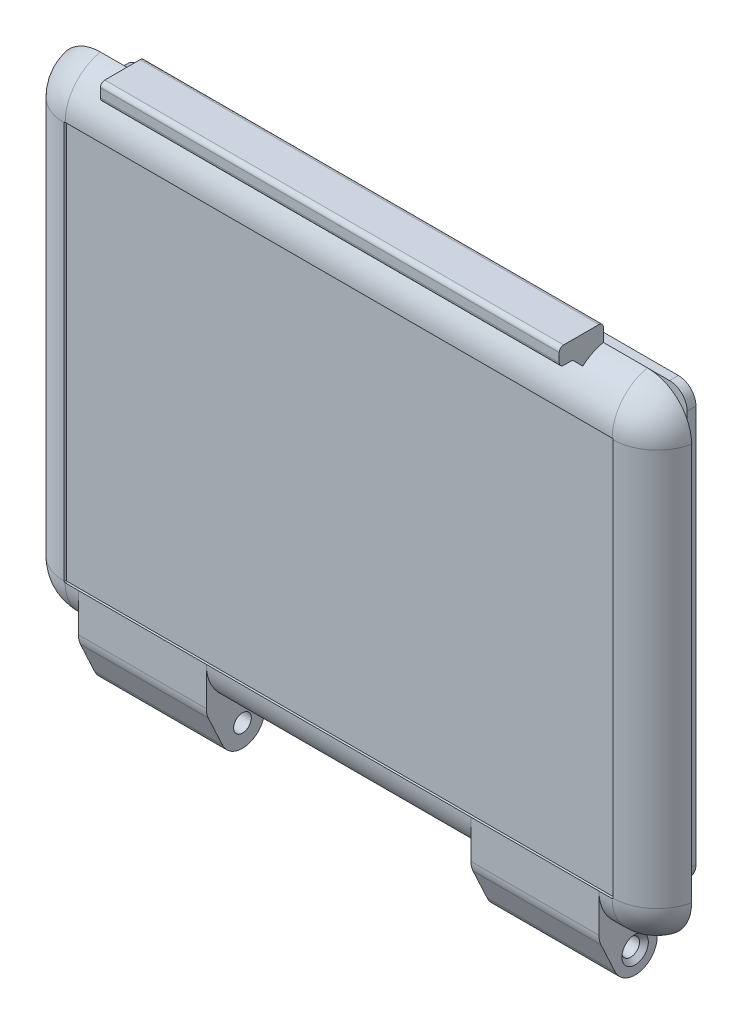
SolidWorks part; units mm, degrees
material "Acrylic (Medium-high impact)"
ref_plane "Front" through (0, 0, 0) normal (0, 0, 1) x (1, 0, 0)
ref_plane "Top" through (0, 0, 0) normal (0, 1, 0) x (1, 0, 0)
ref_plane "Right" through (0, 0, 0) normal (1, 0, 0) x (0, 0, -1)
sketch "Sketch1" plane through (0, 0, 0) normal (0, 0, 1) x (1, 0, 0)
  line L1 (-36, -27.5) -> (36, -27.5)
  line L2 (-36, -27.5) -> (-36, 27.5)
  line L3 (-36, 27.5) -> (36, 27.5)
  line L4 (36, -27.5) -> (36, 27.5)
  line L5 (-36, -27.5) -> (36, 27.5) construction
  line L6 (-36, 27.5) -> (36, -27.5) construction
  point P0 (0, 0)
  dimension "D1" = 72
  dimension "D2" = 55
extrude "Boss-Extrude1" add sketch "Sketch1" along normal blind 4
fillet "Fillet3" radius 5 4 edges at (-36, 27.5, 2) (36, -27.5, 2) (-36, -27.5, 2) (36, 27.5, 2)
fillet "Fillet4" radius 5 8 edges at (34.5355, 26.0355, 4) (36, 0, 4) (34.5355, -26.0355, 4) (0, -27.5, 4) (-34.5355, -26.0355, 4) (-36, 0, 4) (-34.5355, 26.0355, 4) (0, 27.5, 4)
sketch "Sketch2" plane through (0, 0, 4) normal (0, 0, 1) x (1, 0, 0)
  line L4 (31.101, -22.5) -> (31.101, 22.5)
  line L5 (31.101, -22.5) -> (31.101, 22.5)
  line L6 (31, 22.601) -> (-31, 22.601)
  line L7 (31, 22.601) -> (-31, 22.601)
  line L8 (-31.101, 22.5) -> (-31.101, -22.5)
  line L9 (-31.101, 22.5) -> (-31.101, -22.5)
  line L10 (-31, -22.601) -> (31, -22.601)
  line L11 (-31, -22.601) -> (31, -22.601)
  arc A4 (31.101, 22.5) -> (31, 22.601) centre (31, 22.5) ccw
  arc A5 (31.101, 22.5) -> (31, 22.601) centre (31, 22.5) ccw
  arc A6 (-31, 22.601) -> (-31.101, 22.5) centre (-31, 22.5) ccw
  arc A7 (-31, 22.601) -> (-31.101, 22.5) centre (-31, 22.5) ccw
  arc A8 (-31.101, -22.5) -> (-31, -22.601) centre (-31, -22.5) ccw
  arc A9 (-31.101, -22.5) -> (-31, -22.601) centre (-31, -22.5) ccw
  arc A10 (31, -22.601) -> (31.101, -22.5) centre (31, -22.5) ccw
  arc A11 (31, -22.601) -> (31.101, -22.5) centre (31, -22.5) ccw
  dimension "D1" = 0
extrude "Cut-Extrude1" cut sketch "Sketch2" against normal blind 0.25
sketch "Sketch3" plane through (0, 0, 0) normal (0, 0, -1) x (-1, 0, 0)
  line L0 (-31, 23) -> (31, 23)
  line L1 (-30, -22) -> (30, -22)
  line L2 (-30, -22) -> (-30, 22)
  line L3 (-30, 22) -> (30, 22)
  line L4 (30, -22) -> (30, 22)
  line L5 (-30, -22) -> (30, 22) construction
  line L6 (-30, 22) -> (30, -22) construction
  line L7 (31, -23) -> (31, 23)
  line L8 (-31, -23) -> (31, -23)
  line L9 (-31, -23) -> (-31, 23)
  point P0 (0, 0)
  dimension "D1" = 60
  dimension "D2" = 44
  dimension "D3" = 1
extrude "Boss-Extrude2" add sketch "Sketch3" along normal blind 4
sketch "Sketch4" plane through (0, 0, -4) normal (0, 0, -1) x (-1, 0, 0)
  line L4 (30, 22) -> (-30, 22) construction
  line L5 (-30, 22) -> (-30, -22) construction
  line L6 (30, -22) -> (30, 22) construction
  line L7 (-30, -22) -> (30, -22) construction
  line L8 (-32.5, 24.5) -> (-32.5, -24.5)
  line L9 (-32.5, -24.5) -> (32.5, -24.5)
  line L10 (32.5, -24.5) -> (32.5, 24.5)
  line L11 (32.5, 24.5) -> (-32.5, 24.5)
  line L12 (-32.5, 24.5) -> (-32.5, -24.5)
  line L13 (-32.5, -24.5) -> (32.5, -24.5)
  line L14 (32.5, -24.5) -> (32.5, 24.5)
  line L15 (32.5, 24.5) -> (-32.5, 24.5)
  line L16 (30, 22) -> (-30, 22)
  line L17 (-30, 22) -> (-30, -22)
  line L18 (30, -22) -> (30, 22)
  line L19 (-30, -22) -> (30, -22)
  dimension "D1" = 1.5
extrude "Boss-Extrude3" add sketch "Sketch4" against normal blind 1
fillet "Fillet2" radius 2 12 edges at (30, -22, -2) (-30, -22, -2) (-30, 22, -2) (30, 22, -2) (32.5, 24.5, -3.5) (-32.5, 24.5, -3.5) (-32.5, -24.5, -3.5) (32.5, -24.5, -3.5) (-31, -23, -1.5) (31, -23, -1.5) (31, 23, -1.5) (-31, 23, -1.5)
sketch "Sketch5" plane through (0, 0, 0) normal (0, 0, -1) x (-1, 0, 0)
  line L0 (-15, 7) -> (15, 7)
  line L1 (15, -7) -> (-15, -7)
  line L2 (0, 7) -> (0, -7) construction
  line L3 (-15, 5.5) -> (15, 5.5)
  line L4 (15, -5.5) -> (-15, -5.5)
  arc A0 (-15, 7) -> (-15, -7) centre (-15, 0) ccw
  arc A1 (15, -7) -> (15, 7) centre (15, 0) ccw
  arc A2 (15, -5.5) -> (15, 5.5) centre (15, 0) ccw
  arc A3 (-15, 5.5) -> (-15, -5.5) centre (-15, 0) ccw
  point P8 (0, -7)
  point P10 (0, 0)
  dimension "D2" = 14
  dimension "D3" = 1.5
  dimension "D1" = 30
extrude "Boss-Extrude4" add sketch "Sketch5" along normal blind 0.5
sketch "Sketch6" plane through (0, 0, 0) normal (1, 0, 0) x (0, 0, -1)
  line L0 (0, 27.5) -> (0, 29)
  line L1 (-0.5, 29.5) -> (-4.5, 29.5)
  line L2 (-5, 29) -> (-5, 28)
  line L3 (-4.5, 27.5) -> (-3.7071, 27.5)
  line L4 (-3.3536, 27.3536) -> (-1.9485, 25.9485)
  line L5 (-1.9485, 25.9485) -> (0, 25.9485)
  line L6 (0, 22.5) -> (0, 27.5) construction
  line L7 (0, 25.9485) -> (0, 27.5)
  arc A0 (-5, 28) -> (-4.5, 27.5) centre (-4.5, 28) ccw
  arc A1 (0, 29) -> (-0.5, 29.5) centre (-0.5, 29) ccw
  arc A2 (-3.7071, 27.5) -> (-3.3536, 27.3536) centre (-3.7071, 27) cw
  arc A3 (-4.5, 29.5) -> (-5, 29) centre (-4.5, 29) ccw
  point P13 (-5, 27.5)
  point P16 (0, 29.5)
  point P19 (-3.5, 27.5)
  point P22 (-5, 29.5)
  dimension "D6" = 0.5
  dimension "D1" = 5
  dimension "D2" = 2
  dimension "D3" = 3.5
  dimension "D4" = 45
  dimension "D5" = 2
extrude "Boss-Extrude5" add sketch "Sketch6" along normal mid plane 52
sketch "Sketch7" plane through (0, 0, 0) normal (1, 0, 0) x (0, 0, -1)
  line L1 (0, -27.5) -> (0, -22.5) construction
  line L2 (-2.1681, -31.4515) -> (-3.7681, -28.0002)
  line L3 (-4, -26.9487) -> (-4, -22.601)
  line L4 (-4, -22.5) -> (-4, 22.5) construction
  line L5 (0, -27.5) -> (0.1, -27.9)
  circle A0 centre (0.1, -30.4) radius 1
  arc A1 (-2.1681, -31.4515) -> (0.1, -27.9) centre (0.1, -30.4) ccw
  arc A2 (-4, -22.601) -> (0, -27.5) centre (1, -22.601) ccw construction
  arc A3 (-3.7681, -28.0002) -> (-4, -26.9487) centre (-1.5, -26.9487) cw
  arc A4 (-4, -22.601) -> (0, -27.5) centre (1, -22.601) ccw
  point P16 (-4, -27.5)
  dimension "D1" = 5
  dimension "D2" = 2
  dimension "D5" = 2.5
  dimension "D3" = 0.1
  dimension "D4" = 2.9
extrude "Boss-Extrude6" add sketch "Sketch7" along normal mid plane 59
sketch "Sketch8" plane through (0, 0, 0) normal (1, 0, 0) x (0, 0, -1)
  line L3 (0.1, -27.9) -> (0, -27.5)
  line L4 (-4, -22.601) -> (-4, -26.9487)
  line L5 (-3.7681, -28.0002) -> (-2.1681, -31.4515)
  line L6 (0.1, -27.9) -> (0, -27.5)
  line L7 (-4, -22.601) -> (-4, -26.9487)
  line L8 (-3.7681, -28.0002) -> (-2.1681, -31.4515)
  arc A3 (-2.1681, -31.4515) -> (0.1, -27.9) centre (0.1, -30.4) ccw
  arc A4 (-4, -22.601) -> (0, -27.5) centre (1, -22.601) ccw
  arc A5 (-4, -26.9487) -> (-3.7681, -28.0002) centre (-1.5, -26.9487) ccw
  arc A6 (-2.1681, -31.4515) -> (0.1, -27.9) centre (0.1, -30.4) ccw
  arc A7 (-4, -22.601) -> (0, -27.5) centre (1, -22.601) ccw
  arc A8 (-4, -26.9487) -> (-3.7681, -28.0002) centre (-1.5, -26.9487) ccw
  dimension "D1" = 0
extrude "Cut-Extrude2" cut sketch "Sketch8" against normal mid plane 30
chamfer "Chamfer1" distance 0.5 angle 45 2 edges at (29.5, -30.4, -1.1) (-29.5, -30.4, -1.1)
